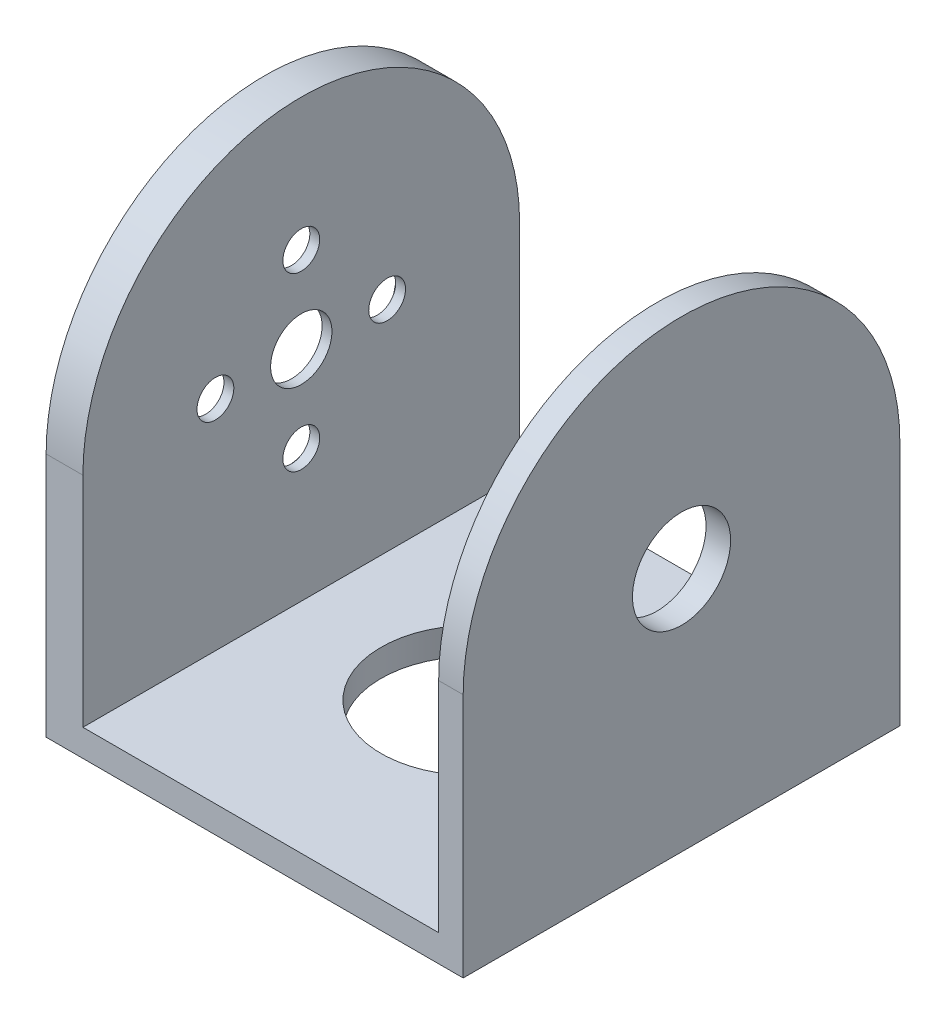
SolidWorks part; units mm, degrees
ref_plane "Front Plane" through (0, 0, 0) normal (0, 0, 1) x (1, 0, 0)
ref_plane "Top Plane" through (0, 0, 0) normal (0, 1, 0) x (1, 0, 0)
ref_plane "Right Plane" through (0, 0, 0) normal (1, 0, 0) x (0, 0, -1)
sketch "Sketch1" plane through (0, 0, 0) normal (0, 1, 0) x (1, 0, 0)
  line L1 (-17, -17.8) -> (17, -17.8)
  line L2 (-17, -17.8) -> (-17, 17.8)
  line L3 (-17, 17.8) -> (17, 17.8)
  line L4 (17, -17.8) -> (17, 17.8)
  line L5 (-17, -17.8) -> (17, 17.8) construction
  line L6 (-17, 17.8) -> (17, -17.8) construction
  point P0 (0, 0)
  dimension "D1" = 35.6
  dimension "D2" = 34
extrude "Boss-Extrude1" add sketch "Sketch1" along normal blind 2.2
sketch "Sketch3" plane through (-17, 0, 0) normal (-1, 0, 0) x (0, 0, 1)
  line L0 (0, 0) -> (0, 37.8) construction
  line L1 (-17.8, 2.2) -> (-17.8, 20)
  line L2 (17.8, 2.2) -> (17.8, 20)
  line L3 (-17.8, 2.2) -> (18.167, 2.2)
  arc A0 (-17.8, 20) -> (17.8, 20) centre (0, 20) cw
  line M3 (17.8, 2.2) -> (-17.8, 2.2)
  dimension "D1" = 17.8
extrude "Boss-Extrude2" add sketch "Sketch3" against normal blind 3 contours L0 L2 A0 M3 | L3 L0 A0 L1 region at (-17, 18.3384, -8.3081) region at (-17, 18.3384, 8.3081)
extrude "Boss-Extrude3" add sketch "Sketch3<4>" along normal blind 2 from surface contours L3 L0 A0 L1 | L0 L2 A0 M3 region at (-17, 18.3384, -8.3081) region at (-17, 18.3384, 8.3081) starting at face at (17, 1.1, 0)
sketch "Sketch3<4>" plane through (-17, 0, 0) normal (-1, 0, 0) x (0, 0, 1) same geometry as "Sketch3"
sketch "Sketch4" plane through (-17, 0, 0) normal (-1, 0, 0) x (0, 0, 1)
  line L0 (0, 37.8) -> (0, 0) construction
  line L1 (-17.8, 0) -> (17.8, 0) construction
  line L2 (-10.925, 20) -> (10.925, 20) construction
  circle A0 centre (0, 20) radius 10.925
  arc A1 (17.8, 20) -> (-17.8, 20) centre (0, 20) ccw construction
  circle A2 centre (0, 27) radius 1.5
  circle A3 centre (0, 13) radius 1.5
  circle A4 centre (-7, 20) radius 1.5
  circle A5 centre (7, 20) radius 1.5
  circle A6 centre (0, 20) radius 2.5
  dimension "D1" = 21.85
  dimension "D2" = 3
  dimension "D3" = 3
  dimension "D4" = 3
  dimension "D5" = 3
  dimension "D6" = 5
  dimension "D7" = 7
  dimension "D8" = 7
  dimension "D9" = 7
  dimension "D10" = 7
extrude "Cut-Extrude1" cut sketch "Sketch4" against normal blind 12 contours A6 | A5 | A2 | A4 | A3 region at (-17, 27, 0) region at (-17, 13, 0) region at (-17, 20, -7) region at (-17, 20, 7) region at (-17, 20, 0)
extrude "Cut-Extrude2" cut sketch "Sketch4<3>" against normal blind 2.2
sketch "Sketch4<3>" plane through (-17, 0, 0) normal (-1, 0, 0) x (0, 0, 1) same geometry as "Sketch4"
sketch "Sketch5" plane through (17, 0, 0) normal (1, 0, 0) x (0, 0, -1)
  line L0 (0, 37.8) -> (0, 0) construction
  arc A0 (17.8, 20) -> (-17.8, 20) centre (0, 20) ccw construction
  circle A1 centre (0, 20) radius 4
  dimension "D1" = 8
extrude "Cut-Extrude3" cut sketch "Sketch5" against normal blind 12.2
sketch "Sketch6" plane through (0, 0, 0) normal (0, -1, 0) x (1, 0, 0)
  circle A0 centre (0, 0) radius 7.5
  dimension "D1" = 15
extrude "Cut-Extrude4" cut sketch "Sketch6" against normal through all both and the other way through all
